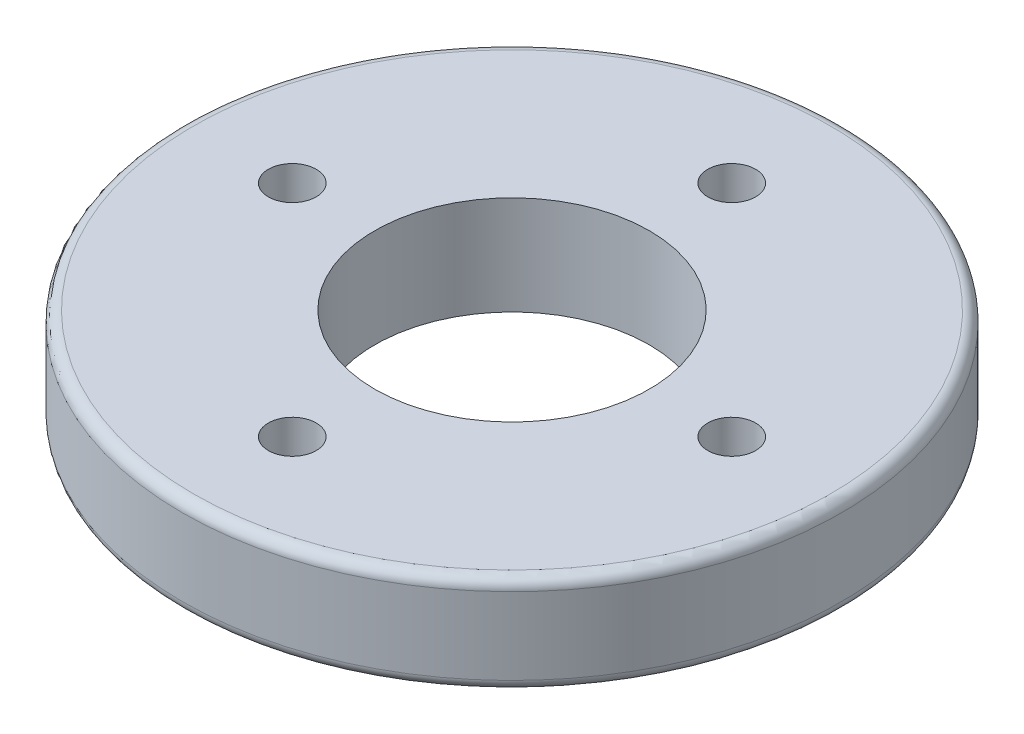
SolidWorks part; units mm, degrees
ref_plane "Front" through (0, 0, 0) normal (0, 0, 1) x (1, 0, 0)
ref_plane "Top" through (0, 0, 0) normal (0, 1, 0) x (1, 0, 0)
ref_plane "Right" through (0, 0, 0) normal (1, 0, 0) x (0, 0, -1)
sketch "Sketch1" plane through (0, 0, 0) normal (0, 1, 0) x (1, 0, 0)
  circle A0 centre (0, 0) radius 15
  dimension "D1" = 30
extrude "Boss-Extrude1" add sketch "Sketch1" along normal blind 4.5
sketch "Sketch2" plane through (0, 4.5, 0) normal (0, 1, 0) x (1, 0, 0)
  line L0 (0, 0) -> (0, 15) construction
  circle A0 centre (0, 0) radius 15 construction
  circle A1 centre (0, 10) radius 1.09
  dimension "D1" = 2.18
  dimension "D2" = 10
extrude "Cut-Extrude1" cut sketch "Sketch2" against normal up to surface (4.5 mm away) up to face at (0, 0, 15)
sketch "Sketch3" plane through (0, 4.5, 0) normal (0, 1, 0) x (1, 0, 0)
  point P0 (0, 0)
sketch "Sketch4" plane through (0, 0, 0) normal (0, 0, 1) x (1, 0, 0)
  line L0 (0, 0) -> (0, 4.5) construction
pattern_circular "CirPattern1" count 4 over 360 about axis through (0, 0, 0) along (0, 1, 0) of "Cut-Extrude1"
fillet "Fillet1" radius 0.5 2 edges at (0, 0, 15) (0, 4.5, 15)
sketch "Sketch5" plane through (0, 4.5, 0) normal (0, 1, 0) x (1, 0, 0)
  circle A0 centre (0, 0) radius 6.25
  dimension "D1" = 12.5
extrude "Cut-Extrude2" cut sketch "Sketch5" against normal mid plane 50
